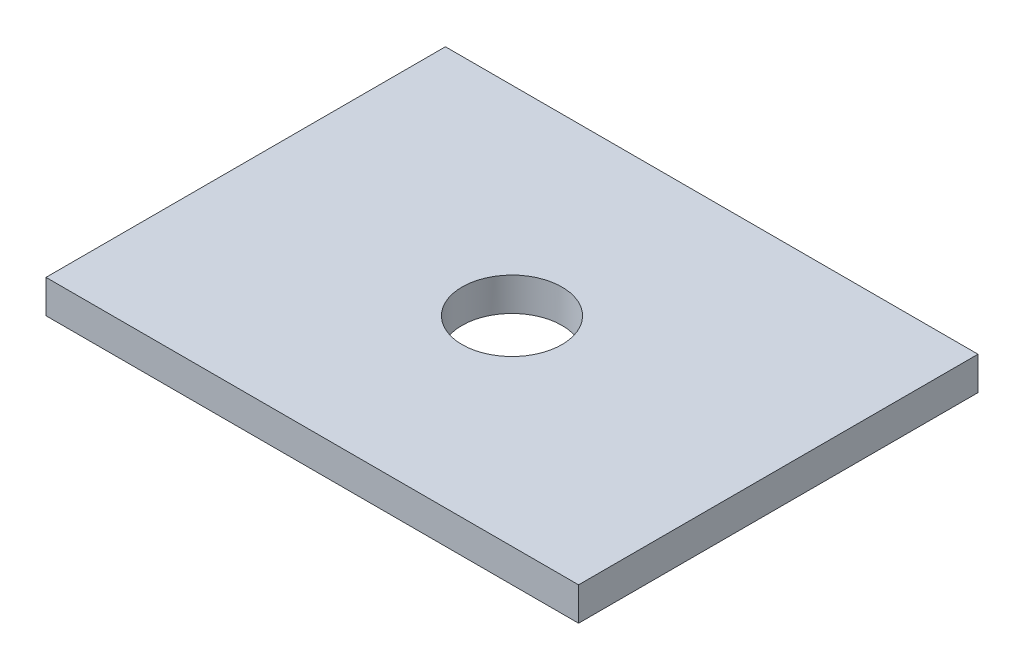
SolidWorks part; units mm, degrees
ref_plane "Front Plane" through (0, 0, 0) normal (0, 0, 1) x (1, 0, 0)
ref_plane "Top Plane" through (0, 0, 0) normal (0, 1, 0) x (1, 0, 0)
ref_plane "Right Plane" through (0, 0, 0) normal (1, 0, 0) x (0, 0, -1)
sketch "Sketch1" plane through (0, 0, 0) normal (0, 1, 0) x (1, 0, 0)
  line L1 (80, 60) -> (-80, 60)
  line L2 (80, 60) -> (80, -60)
  line L3 (80, -60) -> (-80, -60)
  line L4 (-80, 60) -> (-80, -60)
  line L5 (80, 60) -> (-80, -60) construction
  line L6 (80, -60) -> (-80, 60) construction
  point P0 (0, 0)
  dimension "D1" = 160
  dimension "D2" = 120
extrude "base" add sketch "Sketch1" along normal blind 10 contours L1 L4 L3 L2
sketch "Sketch2" plane through (0, 10, 0) normal (0, 1, 0) x (1, 0, 0)
  circle A0 centre (0, 0) radius 15
  dimension "D1" = 30
extrude "actuator cut" cut sketch "Sketch2" against normal blind 40
